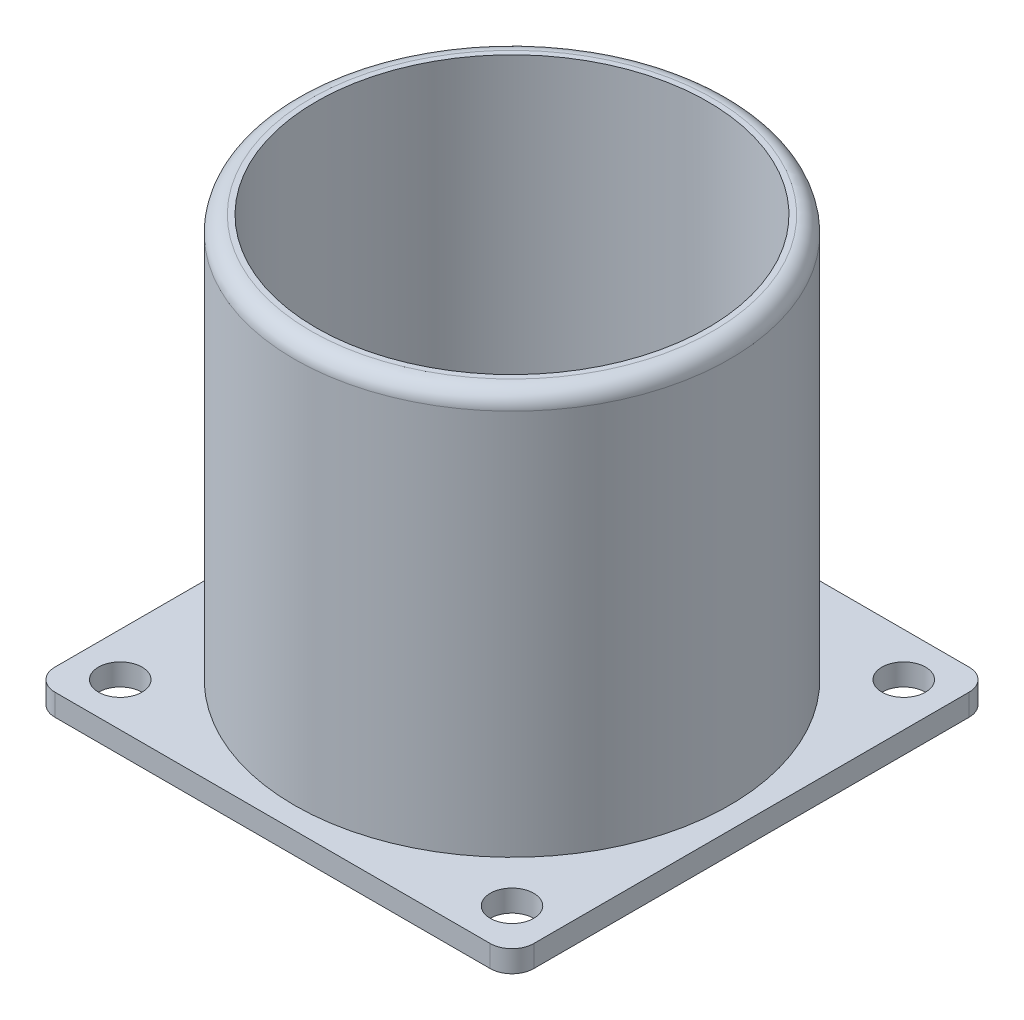
SolidWorks part; units mm, degrees
ref_plane "Plano frontal" through (0, 0, 0) normal (0, 0, 1) x (1, 0, 0)
ref_plane "Plano superior" through (0, 0, 0) normal (0, 1, 0) x (1, 0, 0)
ref_plane "Plano direito" through (0, 0, 0) normal (1, 0, 0) x (0, 0, -1)
sketch "Esboço1" plane through (0, 0, 0) normal (0, 1, 0) x (1, 0, 0)
  line L0 (0, 0) -> (0, 18) construction
  line L1 (-22, -22) -> (22, -22)
  line L2 (-22, -22) -> (-22, 22)
  line L3 (-22, 22) -> (22, 22)
  line L4 (22, -22) -> (22, 22)
  line L5 (-22, -22) -> (22, 22) construction
  line L6 (-22, 22) -> (22, -22) construction
  line L7 (-22, -18) -> (-18, -18) construction
  line L8 (-22, -18) -> (-22, -22) construction
  line L9 (-22, -22) -> (-18, -22) construction
  line L10 (-18, -18) -> (-18, -22) construction
  line L11 (-22, -18) -> (-18, -22) construction
  line L12 (-22, -22) -> (-18, -18) construction
  line L13 (0, 0) -> (8.3253, 0) construction
  line L14 (0.75, -17.9844) -> (0.75, 18)
  line L15 (-18, -18) -> (-16, -18) construction
  line L16 (-18, -18) -> (-18, -16) construction
  line L17 (-18, 18) -> (-6.75, 18) construction
  line L18 (18, -18) -> (18, 18) construction
  line L19 (-18, -18) -> (18, 18) construction
  line L20 (-18, 18) -> (18, -18) construction
  line L21 (-0.75, -17.9844) -> (-0.75, 18)
  line L22 (-0.75, 0) -> (-0.75, 22) construction
  line L23 (0.75, 0) -> (0.75, 22) construction
  line L24 (0.75, 18) -> (0.75, 22) construction
  line L25 (0, 17.7309) -> (0, 22) construction
  line L26 (0, 0) -> (0, 22) construction
  line L27 (-0.75, 18) -> (-0.75, 22) construction
  line L28 (0.75, -17.9844) -> (0.75, 18)
  line L29 (2.25, -17.9844) -> (2.25, 18)
  line L30 (2.25, -17.9844) -> (2.25, 18)
  line L31 (3.75, -17.9844) -> (3.75, 18)
  line L32 (3.75, -17.9844) -> (3.75, 18)
  line L33 (5.25, -17.9844) -> (5.25, 18)
  line L34 (5.25, -17.9844) -> (5.25, 18)
  line L35 (6.75, -17.9844) -> (6.75, 18)
  line L36 (6.75, -17.9844) -> (6.75, 18)
  line L37 (8.25, -17.9844) -> (8.25, 18)
  line L38 (8.25, -17.9844) -> (8.25, 18)
  line L39 (9.75, -17.9844) -> (9.75, 18)
  line L40 (9.75, -17.9844) -> (9.75, 18)
  line L41 (11.25, -17.9844) -> (11.25, 18)
  line L42 (11.25, -17.9844) -> (11.25, 18)
  line L43 (12.75, -17.9844) -> (12.75, 18)
  line L44 (12.75, -17.9844) -> (12.75, 18)
  line L45 (14.25, -17.9844) -> (14.25, 18)
  line L46 (14.25, -17.9844) -> (14.25, 18)
  line L47 (15.75, -17.9844) -> (15.75, 18)
  line L48 (15.75, -17.9844) -> (15.75, 18)
  line L49 (17.25, -17.9844) -> (17.25, 18)
  line L50 (-0.75, -17.9844) -> (0.75, -17.9844) construction
  line L51 (-0.75, 18) -> (0, 18) construction
  line L52 (0.75, 18) -> (2.25, 18) construction
  line L53 (0, 18) -> (0.75, 18) construction
  line L54 (-16, -18) -> (0, -18) construction
  line L55 (16, -18) -> (18, -18) construction
  line L56 (0, -18) -> (16, -18) construction
  line L57 (2.25, 18) -> (3.75, 18) construction
  line L58 (3.75, 18) -> (5.25, 18) construction
  line L59 (5.25, 18) -> (6.75, 18) construction
  line L60 (6.75, 18) -> (18, 18) construction
  line L61 (-17.25, -17.9844) -> (-17.25, 18)
  line L62 (-15.75, -17.9844) -> (-15.75, 18)
  line L63 (-14.25, -17.9844) -> (-14.25, 18)
  line L64 (-12.75, -17.9844) -> (-12.75, 18)
  line L65 (-11.25, -17.9844) -> (-11.25, 18)
  line L66 (-9.75, -17.9844) -> (-9.75, 18)
  line L67 (-8.25, -17.9844) -> (-8.25, 18)
  line L68 (-6.75, -17.9844) -> (-6.75, 18)
  line L69 (-5.25, -17.9844) -> (-5.25, 18)
  line L70 (-3.75, -17.9844) -> (-3.75, 18)
  line L71 (-2.25, -17.9844) -> (-2.25, 18)
  line L72 (-3.75, 18) -> (-2.25, 18) construction
  line L73 (-2.25, 18) -> (-0.75, 18) construction
  line L74 (-6.75, 18) -> (-5.25, 18) construction
  line L75 (-5.25, 18) -> (-3.75, 18) construction
  line L76 (-18, 0) -> (-18, 16) construction
  line L77 (-18, 16) -> (-18, 18) construction
  line L78 (-18, -16) -> (-18, 0) construction
  arc A0 (-0.75, 17.9844) -> (-2.25, 17.8588) centre (0, 0) ccw
  circle A1 centre (-18, -18) radius 2
  circle A2 centre (18, -18) radius 2
  circle A3 centre (18, 18) radius 2
  circle A4 centre (-18, 18) radius 2
  arc A5 (0, 18) -> (-0.75, 17.9844) centre (0, 0) ccw construction
  arc A6 (0.75, 17.9844) -> (0, 18) centre (0, 0) ccw construction
  arc A7 (-0.75, -17.9844) -> (0, -18) centre (0, 0) ccw construction
  arc A8 (0, -18) -> (2.25, -17.8588) centre (0, 0) ccw
  arc A9 (2.25, -17.8588) -> (3.75, -17.605) centre (0, 0) ccw construction
  arc A10 (3.75, -17.605) -> (5.25, -17.2174) centre (0, 0) ccw
  arc A11 (3.75, 17.605) -> (2.25, 17.8588) centre (0, 0) ccw construction
  arc A12 (2.25, 17.8588) -> (0.75, 17.9844) centre (0, 0) ccw
  arc A13 (6.75, 16.6864) -> (5.25, 17.2174) centre (0, 0) ccw construction
  arc A14 (5.25, 17.2174) -> (3.75, 17.605) centre (0, 0) ccw
  arc A15 (5.25, -17.2174) -> (6.75, -16.6864) centre (0, 0) ccw construction
  arc A16 (6.75, -16.6864) -> (8.25, -15.998) centre (0, 0) ccw
  arc A17 (8.25, -15.998) -> (9.75, -15.1307) centre (0, 0) ccw construction
  arc A18 (9.75, -15.1307) -> (11.25, -14.0512) centre (0, 0) ccw
  arc A19 (9.75, 15.1307) -> (8.25, 15.998) centre (0, 0) ccw construction
  arc A20 (8.25, 15.998) -> (6.75, 16.6864) centre (0, 0) ccw
  arc A21 (12.7279, 12.7279) -> (11.25, 14.0512) centre (0, 0) ccw construction
  arc A22 (11.25, 14.0512) -> (9.75, 15.1307) centre (0, 0) ccw
  arc A23 (11.25, -14.0512) -> (12.7279, -12.7279) centre (0, 0) ccw construction
  arc A24 (12.7279, -12.7279) -> (14.25, -10.9972) centre (0, 0) ccw
  arc A25 (14.25, -10.9972) -> (15.75, -8.7142) centre (0, 0) ccw construction
  arc A26 (15.75, -8.7142) -> (17.25, -5.1417) centre (0, 0) ccw
  arc A27 (15.75, 8.7142) -> (14.25, 10.9972) centre (0, 0) ccw construction
  arc A28 (14.25, 10.9972) -> (12.7279, 12.7279) centre (0, 0) ccw
  arc A29 (18, 0) -> (17.25, 5.1417) centre (0, 0) ccw construction
  arc A30 (17.25, 5.1417) -> (15.75, 8.7142) centre (0, 0) ccw
  arc A31 (17.25, -5.1417) -> (18, 0) centre (0, 0) ccw construction
  arc A32 (-2.25, 17.8588) -> (-3.75, 17.605) centre (0, 0) ccw construction
  arc A33 (-3.75, 17.605) -> (-5.25, 17.2174) centre (0, 0) ccw
  arc A34 (-3.75, -17.605) -> (-2.25, -17.8588) centre (0, 0) ccw construction
  arc A35 (-2.25, -17.8588) -> (-0.75, -17.9844) centre (0, 0) ccw
  arc A36 (-6.75, -16.6864) -> (-5.25, -17.2174) centre (0, 0) ccw construction
  arc A37 (-5.25, -17.2174) -> (-3.75, -17.605) centre (0, 0) ccw
  arc A38 (-5.25, 17.2174) -> (-6.75, 16.6864) centre (0, 0) ccw construction
  arc A39 (-6.75, 16.6864) -> (-8.25, 15.998) centre (0, 0) ccw
  arc A40 (-8.25, 15.998) -> (-9.75, 15.1307) centre (0, 0) ccw construction
  arc A41 (-9.75, 15.1307) -> (-11.25, 14.0512) centre (0, 0) ccw
  arc A42 (-9.75, -15.1307) -> (-8.25, -15.998) centre (0, 0) ccw construction
  arc A43 (-8.25, -15.998) -> (-6.75, -16.6864) centre (0, 0) ccw
  arc A44 (-12.7279, -12.7279) -> (-11.25, -14.0512) centre (0, 0) ccw construction
  arc A45 (-11.25, -14.0512) -> (-9.75, -15.1307) centre (0, 0) ccw
  arc A46 (-11.25, 14.0512) -> (-12.7279, 12.7279) centre (0, 0) ccw construction
  arc A47 (-12.7279, 12.7279) -> (-14.25, 10.9972) centre (0, 0) ccw
  arc A48 (-14.25, 10.9972) -> (-15.75, 8.7142) centre (0, 0) ccw construction
  arc A49 (-15.75, 8.7142) -> (-17.25, 5.1417) centre (0, 0) ccw
  arc A50 (-15.75, -8.7142) -> (-14.25, -10.9972) centre (0, 0) ccw construction
  arc A51 (-14.25, -10.9972) -> (-12.7279, -12.7279) centre (0, 0) ccw
  arc A52 (-17.25, 5.1417) -> (-18, 0) centre (0, 0) ccw construction
  arc A53 (-17.25, -5.1417) -> (-15.75, -8.7142) centre (0, 0) ccw
  arc A54 (-18, 0) -> (-17.25, -5.1417) centre (0, 0) ccw construction
  point P7 (-20, -20)
  dimension "D1" = 36
  dimension "D4" = 4
  dimension "D2" = 44
  dimension "D3" = 4
  dimension "D8" = 1.5
  dimension "D5" = 0.75
  dimension "D6" = 0.75
  dimension "D7" = 12
extrude "Ressalto-extrusão1" add sketch "Esboço1" along normal blind 2 contours L1 L4 L3 L2 A30 A3 L49 A2 A26 L48 A28 L46 A24 L44 A22 L42 A18 L40 A20 region at (0, 0, 0)
ref_plane "Plano1" through (0, 2, 0) normal (0, 1, 0) x (1, 0, 0)
sketch "Esboço3" plane through (0, 2, 0) normal (0, 1, 0) x (1, 0, 0)
  circle A0 centre (0, 0) radius 18
  arc A1 (5.25, 17.2174) -> (3.75, 17.605) centre (0, 0) ccw construction
  circle A2 centre (0, 0) radius 20
  dimension "D1" = 2
extrude "Ressalto-extrusão3" add sketch "Esboço3" along normal blind 37
fillet "Filete3" radius 1.5 1 edges at (0, 39, 20)
fillet "Filete4" radius 2 4 edges at (-22, 1, -22) (-22, 1, 22) (22, 1, 22) (22, 1, -22)
equation "\"D2@Esboço1\"=\"D1@Esboço1\"+8"
